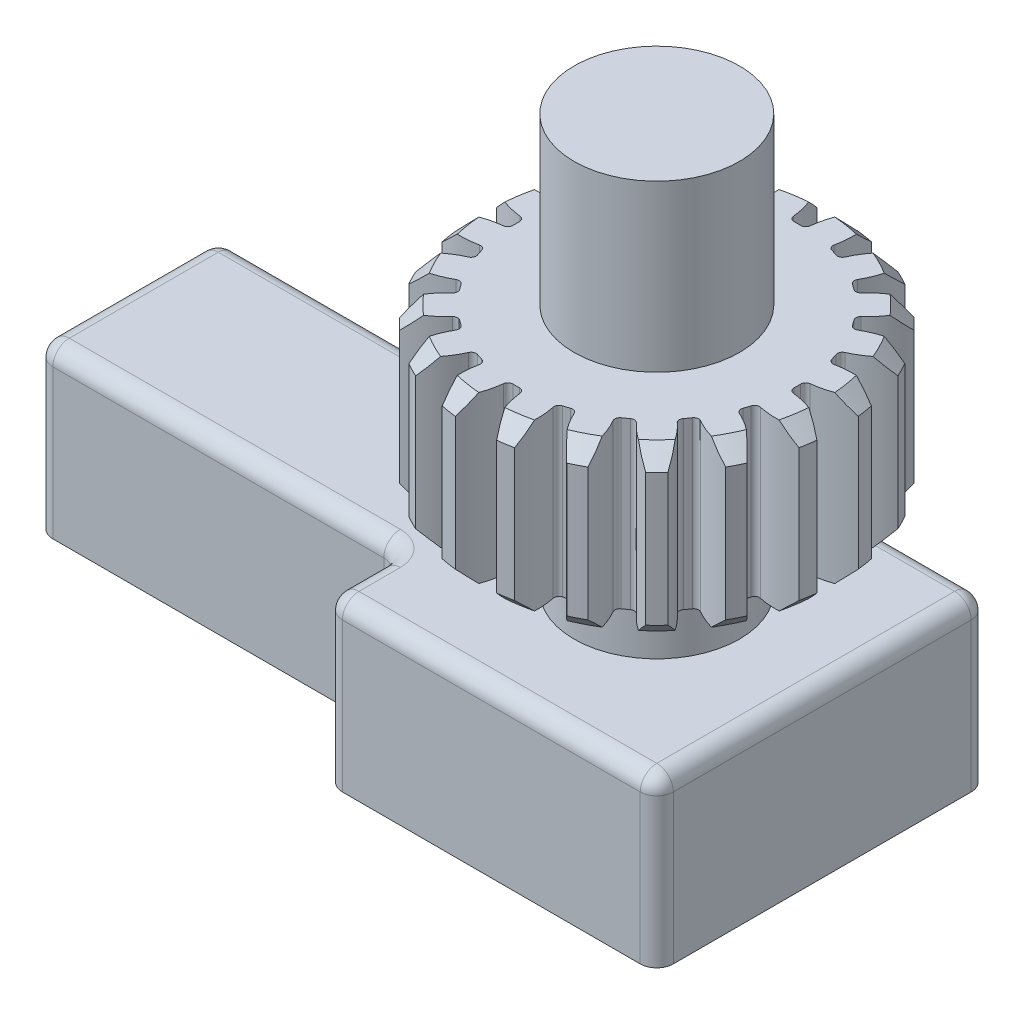
SolidWorks part; units mm, degrees
ref_plane "Front Plane" through (0, 0, 0) normal (0, 0, 1) x (1, 0, 0)
ref_plane "Top Plane" through (0, 0, 0) normal (0, 1, 0) x (1, 0, 0)
ref_plane "Right Plane" through (0, 0, 0) normal (1, 0, 0) x (0, 0, -1)
sketch "Sketch1" plane through (0, 0, 0) normal (0, 1, 0) x (1, 0, 0)
  circle A0 centre (0, 0) radius 10 construction
  circle A1 centre (0, 0) radius 11
  dimension "D1" = 20
  dimension "D2" = 22
extrude "Boss-Extrude1" add sketch "Sketch1" along normal mid plane 10
sketch "Sketch2" plane through (0, 0, 0) normal (0, 1, 0) x (1, 0, 0)
  line L0 (0, 11) -> (0, 0) construction
  line L1 (0, 0) -> (1.7208, 10.8646) construction
  line L2 (0, 0) -> (3.3992, 10.4616) construction
  line L3 (-0.4798, 8.4865) -> (0, 0) construction
  line L4 (-0.7846, 9.9692) -> (0.7846, 9.9692) construction
  line L5 (0.7846, 9.9692) -> (2.3345, 9.7237) construction
  line L6 (-1.1383, 10.9409) -> (0, 7.8135) construction
  circle A0 centre (0, 0) radius 9 construction
  circle A2 centre (0, 0) radius 11 construction
  arc A3 (-1.2504, 10.9287) -> (-0.4798, 8.4865) centre (-5.6635, 8.1934) cw
  arc A4 (1.2504, 10.9287) -> (0.4798, 8.4865) centre (5.6635, 8.1934) ccw
  circle A5 centre (0, 0) radius 10 construction
  arc A6 (0.4798, 8.4865) -> (-0.4798, 8.4865) centre (0, 0) ccw
  arc A7 (-1.2504, 10.9287) -> (1.2504, 10.9287) centre (0, 0) cw
  dimension "D1" = 18
  dimension "D2" = 9
  dimension "D4" = 2
  dimension "D5" = 20
  dimension "D3" = 0.5
extrude "Cut-Extrude4" cut sketch "Sketch2" against normal through all both and the other way through all
fillet "Fillet1" radius 0.3 2 edges at (0.4798, 0, -8.4865) (-0.4798, 0, -8.4865)
chamfer "Chamfer1" distance 1 angle 45 2 edges at (0, 5, 11) (0, -5, 11)
pattern_circular "CirPattern1" count 20 over 360 about axis through (0, 5, 0) along (0, -1, 0) of "Fillet1", "Cut-Extrude4"
sketch "Sketch3" plane through (0, 5, 0) normal (0, 1, 0) x (1, 0, 0)
  circle A0 centre (0, 0) radius 5
  dimension "D1" = 10
extrude "Boss-Extrude2" add sketch "Sketch3" along normal blind 10
sketch "Sketch6" plane through (0, -5, 0) normal (0, -1, 0) x (1, 0, 0)
  circle A0 centre (0, 0) radius 5
  dimension "D1" = 10
extrude "Boss-Extrude3" add sketch "Sketch6" along normal blind 5
sketch "Sketch11" plane through (0, -10, 0) normal (0, -1, 0) x (1, 0, 0)
  line L0 (-32, 0) -> (10, 0) construction
  line L1 (-10, 10) -> (-10, -10)
  line L2 (10, 10) -> (10, -10)
  line L3 (-10, 10) -> (10, 10)
  line L4 (-10, -10) -> (10, -10)
  line L5 (-10, 5.5) -> (-32, 5.5)
  line L6 (-32, 5.5) -> (-32, -5.5)
  line L7 (-32, -5.5) -> (-10, -5.5)
  line L8 (0, 10) -> (0, -10) construction
  line L9 (0, 5) -> (0, -5) construction
  line L10 (-5, 0) -> (5, 0) construction
  circle A0 centre (0, 0) radius 5 construction
  circle A1 centre (0, 0) radius 5 construction
  point P12 (-32, 0)
  point P23 (0, 0)
  point P24 (0, 0)
  circle M9 centre (0, 0) radius 5
  dimension "D1" = 20
  dimension "D2" = 20
  dimension "D3" = 22
  dimension "D4" = 11
extrude "Boss-Extrude5" add sketch "Sketch11" along normal blind 10 contours L1 L4 L2 L3 M9 | L6 L7 L1 L5 | M9 region at (0, -10, 9.7172) region at (-21, -10, 0) region at (0, -10, 0)
sketch "Sketch12" plane through (0, -20, 0) normal (0, -1, 0) x (1, 0, 0)
  line L0 (-45, 0) -> (8.5, 0) construction
  line L1 (-8.5, 8.5) -> (-8.5, -8.5)
  line L2 (8.5, 8.5) -> (8.5, -8.5)
  line L3 (-8.5, 8.5) -> (8.5, 8.5)
  line L4 (-8.5, -8.5) -> (8.5, -8.5)
  line L5 (-8.5, 4) -> (-29.5, 4)
  line L6 (-29.5, 4) -> (-29.5, -4)
  line L7 (-29.5, -4) -> (-8.5, -4)
  line L8 (0, 8.5) -> (0, -8.5) construction
  line L9 (0, -10) -> (0, 10) construction
  line L10 (-10, -10) -> (10, -10) construction
  line L11 (-10, 0) -> (10, 0) construction
  circle A0 centre (0, 0) radius 10 construction
  point P12 (-29.5, 0)
  dimension "D1" = 17
  dimension "D2" = 17
  dimension "D3" = 21
  dimension "D4" = 8
extrude "Cut-Extrude5" cut sketch "Sketch12" against normal blind 6 contours L6 L7 L1 L5 | L1 L4 L2 L3 region at (0, -20, 0) region at (-19, -20, 0)
fillet "Fillet2" radius 1 24 edges at (-10, -10, 7.75) (-10, -10, -7.75) (10, -10, 0) (0, -10, 10) (-21, -10, 5.5) (-32, -10, 0) (-21, -10, -5.5) (0, -10, -10) (10, -15, 10) (-10, -15, 10) (-10, -15, -5.5) (-10, -15, 5.5) (-32, -15, 5.5) (-32, -15, -5.5) (-10, -15, -10) (10, -15, -10) (-8.5, -17, -8.5) (-8.5, -17, -4) (8.5, -17, -8.5) (8.5, -17, 8.5) (-8.5, -17, 8.5) (-8.5, -17, 4) (-29.5, -17, -4) (-29.5, -17, 4)
equation "\"D1@Sketch1\" = \"Module\" * \"Number of Teeth\""
equation "\"D2@Sketch1\" = ( \"Number of Teeth\" + 2 ) * \"Module\""
equation "\"D1@Sketch2\" = 360 / \"Number of Teeth\""
equation "\"D2@Sketch2\" = 180 / \"Number of Teeth\""
equation "\"D4@Sketch2\" = \"Module\" * 2"
equation "\"D5@Sketch2\"= \"Pressure Angle\""
equation "\"D1@Fillet1\" = 0.3 * \"Module\""
equation "\"D1@CirPattern1\" = \"Number of Teeth\""
equation "\"D1@Chamfer1\" = \"Module\""
